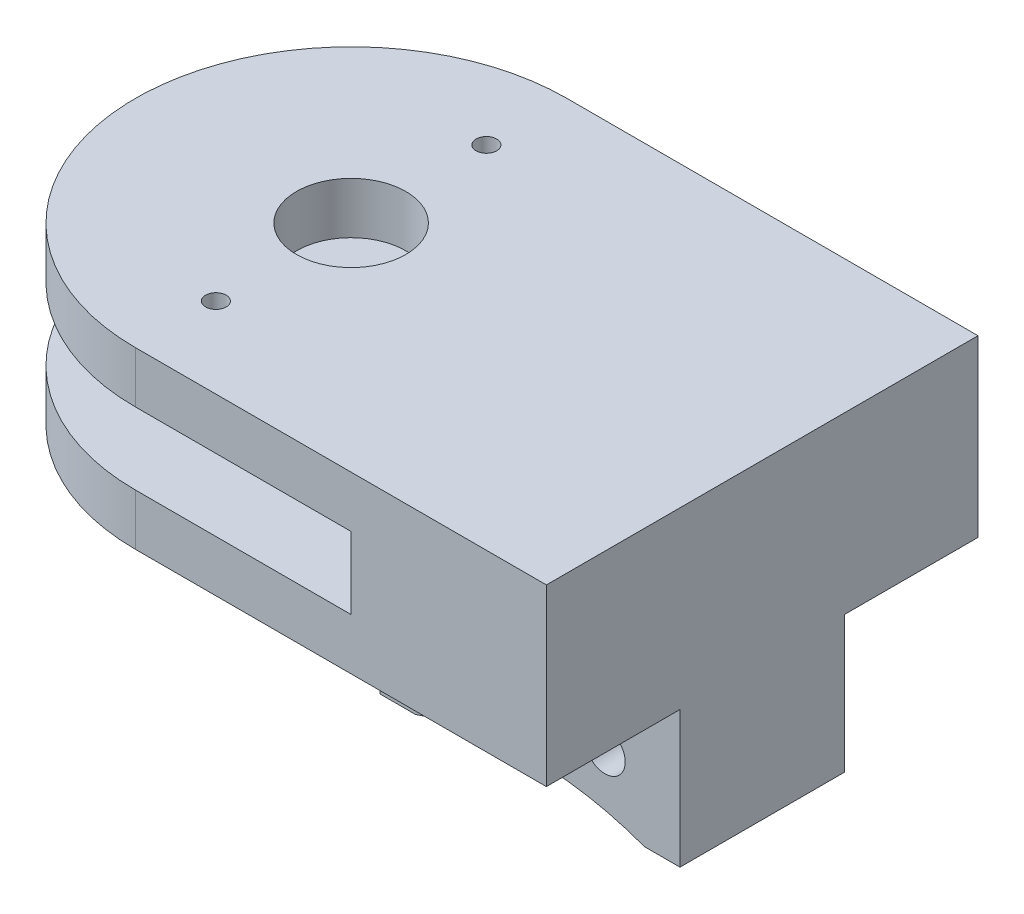
SolidWorks part; units mm, degrees
ref_plane "Front Plane" through (0, 0, 0) normal (0, 0, 1) x (1, 0, 0)
ref_plane "Top Plane" through (0, 0, 0) normal (0, 1, 0) x (1, 0, 0)
ref_plane "Right Plane" through (0, 0, 0) normal (1, 0, 0) x (0, 0, -1)
sketch "Sketch1" plane through (0, 0, 0) normal (0, 1, 0) x (1, 0, 0)
  line L0 (0, -13.335) -> (25.4, -13.335)
  line L1 (0, 13.335) -> (25.4, 13.335)
  line L2 (25.4, 13.335) -> (25.4, -13.335)
  circle A0 centre (0, 0) radius 12.7 construction
  circle A1 centre (0, 0) radius 13.335 construction
  circle A2 centre (0, 0) radius 3.3782
  arc A3 (11.5484, 6.6675) -> (11.5484, -6.6675) centre (0, 0) ccw construction
  arc A4 (0, 13.335) -> (0, -13.335) centre (0, 0) ccw
  dimension "D1" = 25.4
  dimension "D2" = 0.635
  dimension "D4" = 6.7564
  dimension "D3" = 25.4
extrude "Boss-Extrude1" add sketch "Sketch1" along normal blind 3.175 contours A3 A2 region at (7.6257, 0, 0)
sketch "Sketch2" plane through (0, 0, 0) normal (0, -1, 0) x (-1, 0, 0)
  line L3 (-25.4, 13.335) -> (-25.4, -13.335)
  line L5 (-13.335, 0) -> (-13.335, 13.335)
  line L6 (-25.4, 13.335) -> (-13.335, 13.335)
  line L7 (-13.335, 0) -> (-13.335, -13.335)
  line L8 (0, -13.335) -> (-25.4, -13.335) construction
  line L9 (-13.335, -13.335) -> (-25.4, -13.335)
  arc A3 (0, 13.335) -> (0, -13.335) centre (0, 0) ccw construction
extrude "Boss-Extrude2" add sketch "Sketch2" along normal blind 4.445 contours L3 L9 L7 L5 L6
ref_plane "Plane2" through (0, -2.2225, 0) normal (0, -1, 0) x (-1, 0, 0)
mirror "Mirror2" about plane through (0, -2.2225, 0) normal (0, -1, 0) of "Boss-Extrude1"
sketch "Sketch7" plane through (0, -7.62, 0) normal (0, -1, 0) x (-1, 0, 0)
  line L0 (-25.4, 13.335) -> (-25.4, 5.08) construction
  line L1 (-25.4, 13.335) -> (-25.4, -13.335) construction
  line L2 (0, 0) -> (-25.4, 0) construction
  line L3 (-25.4, -13.335) -> (-25.4, -5.08) construction
  line L5 (-25.4, 5.08) -> (-6.858, 5.08)
  line L6 (-25.4, 5.08) -> (-25.4, -5.08)
  line L7 (-25.4, -5.08) -> (-6.858, -5.08)
  line L8 (-6.858, 5.08) -> (-6.858, -5.08)
  dimension "D1" = 8.255
  dimension "D2" = 18.542
extrude "Boss-Extrude4" add sketch "Sketch7" along normal blind 8.4391
sketch "Sketch8" plane through (0, 0, -5.08) normal (0, 0, -1) x (-1, 0, 0)
  line L0 (-16.129, -7.62) -> (-16.129, -16.0591) construction
  line L1 (-16.129, -16.0591) -> (-25.4, -16.0591) construction
  line L2 (-20.7645, -16.0591) -> (-20.7645, -7.62) construction
  line L3 (-6.858, -7.62) -> (-25.4, -7.62) construction
  line L4 (-6.858, -16.0591) -> (-25.4, -16.0591) construction
  line L5 (0, -7.62) -> (-25.4, -7.62) construction
  circle A0 centre (-20.7645, -12.1285) radius 1.25
  circle A1 centre (-11.4935, -12.1285) radius 1.25
  dimension "D1" = 2.5
  dimension "D2" = 4.5085
extrude "Cut-Extrude3" cut sketch "Sketch8" against normal through all
sketch "Sketch9" plane through (0, 0, -5.08) normal (0, 0, -1) x (-1, 0, 0)
  line L0 (-16.129, -16.0591) -> (-16.129, -35.1091) construction
  line L1 (-6.858, -16.0591) -> (-25.4, -16.0591) construction
  line L2 (-16.129, -16.0591) -> (-16.129, -14.7891) construction
  circle A0 centre (-16.129, -35.1091) radius 20.32
  dimension "D1" = 1.27
  dimension "D2" = 19.05
extrude "Cut-Extrude4" cut sketch "Sketch9" against normal through all
sketch "Sketch10" plane through (0, 3.175, 0) normal (0, 1, 0) x (1, 0, 0)
  line L0 (0, 13.335) -> (0, 3.3782) construction
  line L2 (0, 0) -> (25.4, 0) construction
  line L3 (25.4, 13.335) -> (25.4, -13.335) construction
  arc A1 (0, 13.335) -> (0, -13.335) centre (0, 0) ccw construction
  circle A2 centre (0, 0) radius 3.3782 construction
  circle A3 centre (0, 8.3566) radius 0.635
  circle A4 centre (0, -8.3566) radius 0.635
  dimension "D1" = 1.27
extrude "Cut-Extrude5" cut sketch "Sketch10" against normal up to surface (3.175 mm away) up to face at (0, 0, 3.3782)
